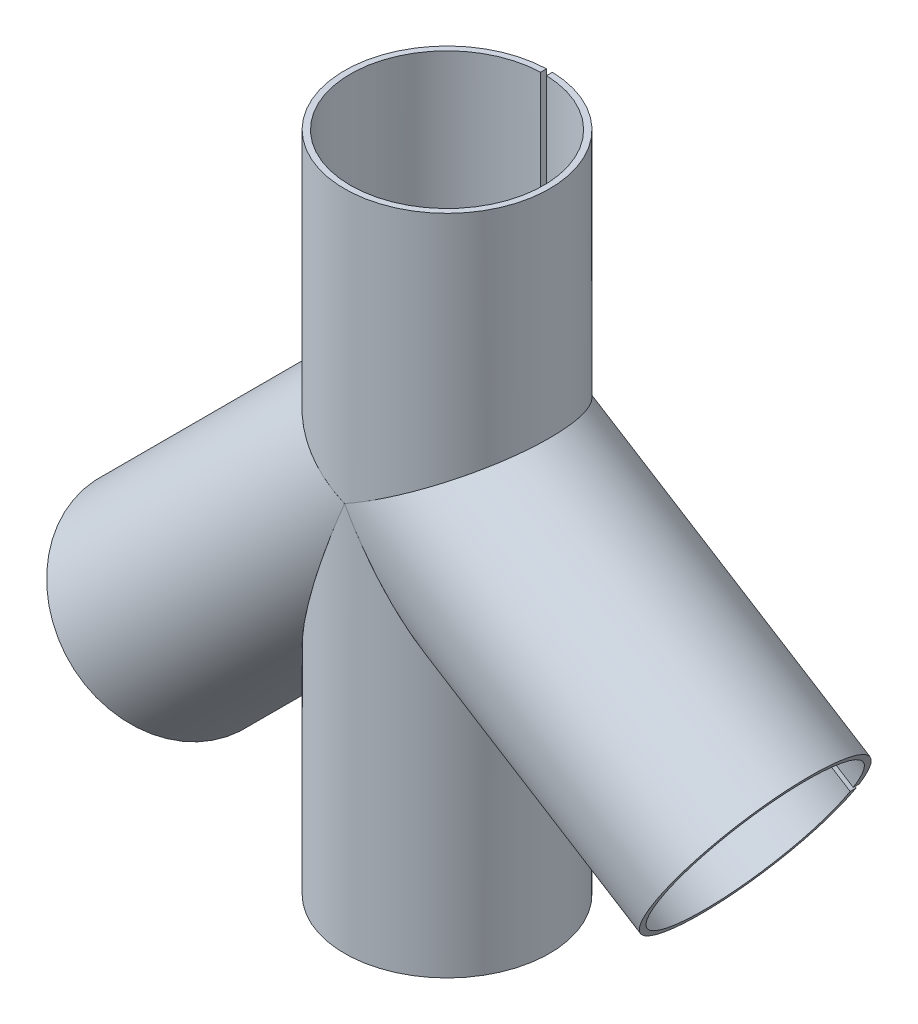
SolidWorks part; units mm, degrees
ref_plane "前视基准面" through (0, 0, 0) normal (0, 0, 1) x (1, 0, 0)
ref_plane "上视基准面" through (0, 0, 0) normal (0, 1, 0) x (1, 0, 0)
ref_plane "右视基准面" through (0, 0, 0) normal (1, 0, 0) x (0, 0, -1)
sketch "草图1" plane through (0, 0, 0) normal (0, 0, 1) x (1, 0, 0)
  line L0 (0, 46.1704) -> (0, 0) construction
  line L1 (0, 0) -> (52.1963, -32.6972) construction
  line L2 (0, -66) -> (0, 0) construction
  line L3 (0, 0) -> (-46.5623, -46.5623) construction
  line L4 (-17.3631, 46.1704) -> (17.3631, 46.1704) construction
  line L5 (-58.8399, -34.2848) -> (-34.2848, -58.8399) construction
  line L6 (-17.3631, -66) -> (17.3631, -66) construction
  line L7 (42.9787, -47.4116) -> (61.4138, -17.9828) construction
  line L8 (0, -66) -> (0, -67) construction
  line L9 (-17.3631, 46.1704) -> (-17.3631, 7.192) construction
  line L10 (-17.3631, 7.192) -> (-58.8399, -34.2848) construction
  line L11 (-34.2848, -58.8399) -> (-17.3631, -41.9182) construction
  line L12 (-17.3631, -41.9182) -> (-17.3631, -66) construction
  line L13 (17.3631, -66) -> (17.3631, -31.3652) construction
  line L14 (17.3631, -31.3652) -> (42.9787, -47.4116) construction
  line L15 (17.3631, 46.1704) -> (17.3631, 9.6118) construction
  line L16 (17.3631, 9.6118) -> (61.4138, -17.9828) construction
  line L17 (0, 0) -> (0, 46.1704)
  line L18 (-17.3631, 7.192) -> (0, 0) construction
  line L19 (0, 0) -> (17.3631, 9.6118) construction
  line L20 (-17.3631, -41.9182) -> (0, 0) construction
  line L21 (0, 0) -> (17.3631, -31.3652) construction
  line L22 (0, 0) -> (52.1963, -32.6972)
  dimension "R" = 17.3631
  dimension "l1" = 46.1704
  dimension "L2" = 65.8491
  dimension "L3" = 66
  dimension "L4" = 61.5918
  dimension "B1" = 45
  dimension "B2" = 57.936
  dimension "t" = 1
sketch "草图2" plane through (0, 0, 0) normal (0, 1, 0) x (1, 0, 0)
  circle A0 centre (0, 0) radius 17.3631
extrude "拉伸-薄壁1" add sketch "草图2" along normal up to vertex (46.1704 mm away) thin up to point (0, 46.1704, 0) thin type one direction reverse wall 1
ref_plane "基准面1" through (52.1963, -32.6972, 0) normal (0.8475, -0.5309, 0) x (0, 0, -1)
ref_plane "基准面2" through (-46.5623, -46.5623, 0) normal (-0.7071, -0.7071, 0) x (0.7071, -0.7071, 0)
sketch "草图3" plane through (52.1963, -32.6972, 0) normal (0.8475, -0.5309, 0) x (0, 0, -1)
  circle A0 centre (0, 0) radius 17.3631
extrude "拉伸-薄壁2" add sketch "草图3" against normal up to vertex (61.5918 mm away) separate body thin up to point (0, 0, 0) thin type one direction reverse wall 1
sketch "草图4" plane through (-46.5623, -46.5623, 0) normal (-0.7071, -0.7071, 0) x (0.7071, -0.7071, 0)
  circle A0 centre (0, 0) radius 17.3631
extrude "拉伸-薄壁3" add sketch "草图4" against normal up to vertex (65.8491 mm away) separate body thin up to point (0, 0, 0) thin type one direction reverse wall 1
sketch "草图5" plane through (0, 0, 0) normal (0, 1, 0) x (1, 0, 0)
  circle A0 centre (0, 0) radius 17.3631
extrude "拉伸-薄壁4" add sketch "草图5" against normal up to vertex (66 mm away) separate body thin up to point (0, -66, 0) thin type one direction reverse wall 1
sketch "草图6" plane through (0, 0, 0) normal (0, 0, 1) x (1, 0, 0)
  line L0 (-17.3631, 7.192) -> (0, 0) construction
  line L1 (0, 0) -> (17.3631, 9.6118) construction
  line L2 (17.3631, 46.1704) -> (17.3631, 9.6118) construction
  line L3 (-17.3631, 46.1704) -> (-17.3631, 7.192) construction
  line L4 (-17.3631, 46.1704) -> (17.3631, 46.1704) construction
  line L5 (-17.3631, 7.192) -> (0, 0)
  line L6 (0, 0) -> (17.3631, 9.6118)
  line L7 (17.3631, 46.1704) -> (17.3631, 9.6118)
  line L8 (-17.3631, 46.1704) -> (-17.3631, 7.192)
  line L9 (-17.3631, 46.1704) -> (17.3631, 46.1704)
extrude "切除-拉伸1" cut sketch "草图6" against normal through all and the other way through all flip side to cut
sketch "草图7" plane through (0, 0, 0) normal (0, 0, 1) x (1, 0, 0)
  line L0 (-17.3631, 7.192) -> (0, 0) construction
  line L1 (-17.3631, -41.9182) -> (0, 0) construction
  line L2 (-58.8399, -34.2848) -> (-34.2848, -58.8399) construction
  line L3 (-17.3631, 7.192) -> (-58.8399, -34.2848) construction
  line L4 (-17.3631, 7.192) -> (0, 0)
  line L5 (-17.3631, -41.9182) -> (0, 0)
  line L6 (-58.8399, -34.2848) -> (-34.2848, -58.8399)
  line L7 (-17.3631, 7.192) -> (-58.8399, -34.2848)
  line L8 (-34.2848, -58.8399) -> (-17.3631, -41.9182) construction
  line L9 (-34.2848, -58.8399) -> (-17.3631, -41.9182)
extrude "切除-拉伸2" cut sketch "草图7" against normal through all and the other way through all flip side to cut
sketch "草图10" plane through (0, 0, 0) normal (0, 0, 1) x (1, 0, 0)
  line L0 (-17.3631, -41.9182) -> (-17.3631, -66) construction
  line L1 (-17.3631, -41.9182) -> (0, 0) construction
  line L2 (0, 0) -> (17.3631, -31.3652) construction
  line L3 (-17.3631, -66) -> (17.3631, -66) construction
  line L4 (17.3631, -66) -> (17.3631, -31.3652) construction
  line L5 (-17.3631, -41.9182) -> (-17.3631, -66)
  line L6 (-17.3631, -41.9182) -> (0, 0)
  line L7 (0, 0) -> (17.3631, -31.3652)
  line L8 (-17.3631, -66) -> (17.3631, -66)
  line L9 (17.3631, -66) -> (17.3631, -31.3652)
extrude "切除-拉伸5" cut sketch "草图10" against normal through all and the other way through all flip side to cut
sketch "草图11" plane through (0, 0, 0) normal (0, 0, 1) x (1, 0, 0)
  line L0 (0, 0) -> (17.3631, -31.3652) construction
  line L1 (17.3631, -31.3652) -> (42.9787, -47.4116) construction
  line L2 (42.9787, -47.4116) -> (61.4138, -17.9828) construction
  line L3 (17.3631, 9.6118) -> (61.4138, -17.9828) construction
  line L4 (0, 0) -> (17.3631, 9.6118) construction
  line L5 (0, 0) -> (17.3631, -31.3652)
  line L6 (17.3631, -31.3652) -> (42.9787, -47.4116)
  line L7 (42.9787, -47.4116) -> (61.4138, -17.9828)
  line L8 (17.3631, 9.6118) -> (61.4138, -17.9828)
  line L9 (0, 0) -> (17.3631, 9.6118)
extrude "切除-拉伸6" cut sketch "草图11" against normal through all and the other way through all flip side to cut
extrude "切除-拉伸-薄壁6" cut sketch "草图1" against normal through all thin thin type mid plane wall 1
sketch "草图12" plane through (0, 0, 0) normal (0, 0, 1) x (1, 0, 0)
  line L0 (0, -66) -> (0, 0) construction
  line L1 (0, 0) -> (-46.5623, -46.5623) construction
  line L2 (0, -66) -> (0, 0)
  line L3 (0, 0) -> (-46.5623, -46.5623)
extrude "切除-拉伸-薄壁7" cut sketch "草图12" against normal through all thin thin type mid plane wall 1
equation "\"D5@拉伸-薄壁1\" = \"t@草图1\""
equation "\"D5@拉伸-薄壁2\" = \"t@草图1\""
equation "\"D5@拉伸-薄壁3\" = \"t@草图1\""
equation "\"D5@拉伸-薄壁4\" = \"t@草图1\""
